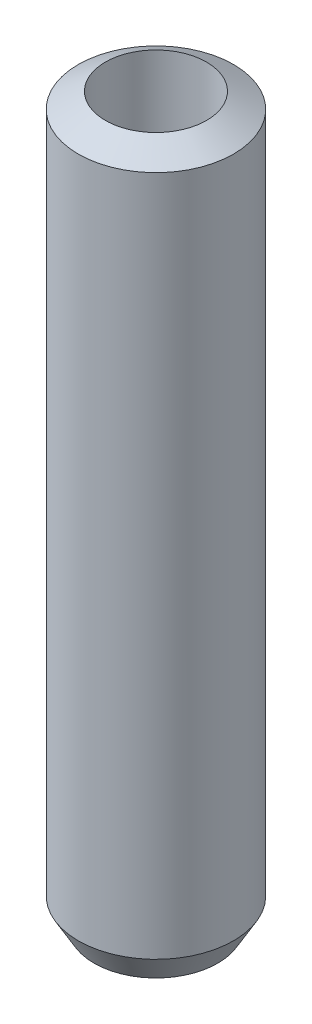
SolidWorks part; units mm, degrees
ref_plane "Front Plane" through (0, 0, 0) normal (0, 0, 1) x (1, 0, 0)
ref_plane "Top Plane" through (0, 0, 0) normal (0, 1, 0) x (1, 0, 0)
ref_plane "Right Plane" through (0, 0, 0) normal (1, 0, 0) x (0, 0, -1)
sketch "Sketch1" plane through (0, 0, 0) normal (0, 1, 0) x (1, 0, 0)
  circle A0 centre (0, 0) radius 7.5
  dimension "SHAFT_OD" = 15
extrude "Boss-Extrude1" add sketch "Sketch1" along normal blind 69.9773
sketch "Sketch2" plane through (0, 0, 0) normal (0, 1, 0) x (1, 0, 0)
  circle A0 centre (0, 0) radius 4.8878
  dimension "BORE_D" = 9.7755
extrude "Cut-Extrude1" cut sketch "Sketch2" along normal through all
chamfer "Chamfer1" distance 1.5246 angle 60 2 edges at (0, 69.9773, 7.5) (0, 0, 7.5) first distance on face at (0, 69.9773, 7.5) first distance on face at (0, 0, 4.8878)
